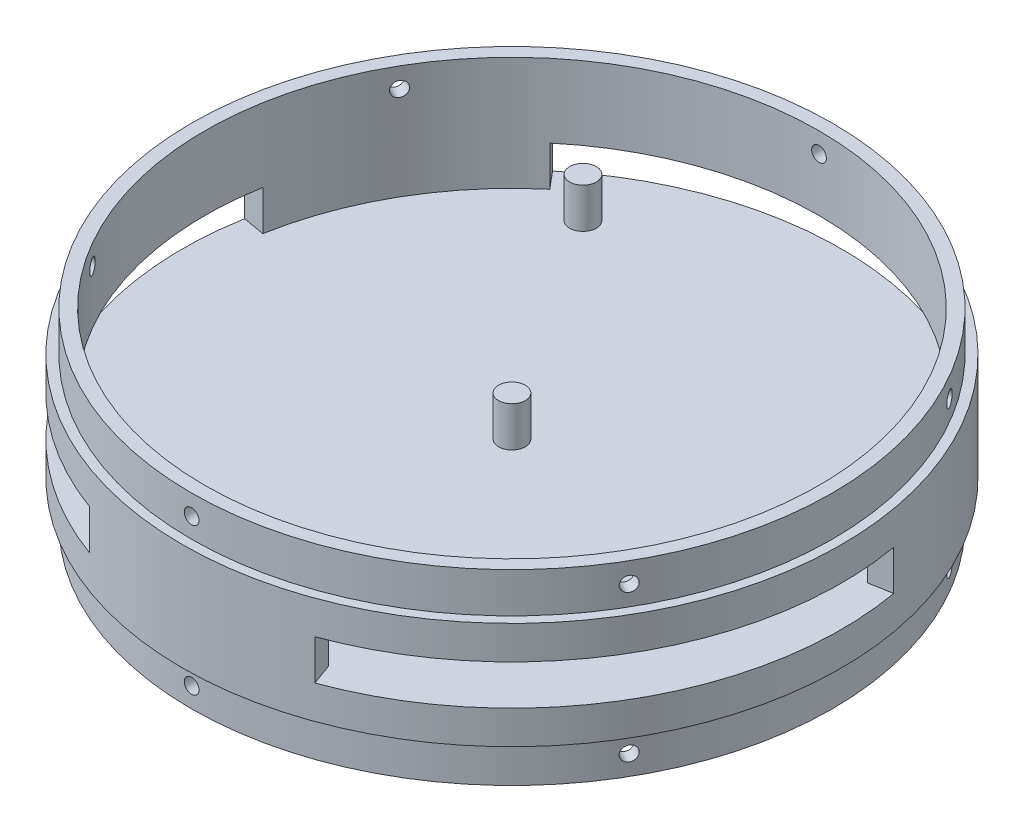
SolidWorks part; units mm, degrees
ref_plane "Front Plane" through (0, 0, 0) normal (0, 0, 1) x (1, 0, 0)
ref_plane "Top Plane" through (0, 0, 0) normal (0, 1, 0) x (1, 0, 0)
ref_plane "Right Plane" through (0, 0, 0) normal (1, 0, 0) x (0, 0, -1)
sketch "Sketch1" plane through (0, 0, 0) normal (0, 1, 0) x (1, 0, 0)
  line L0 (0, 0) -> (-50.3682, 60.0265)
  line L1 (0, 0) -> (50.3682, 60.0265)
  line L2 (0, 0) -> (0, 72.1431) construction
  circle A0 centre (0, 0) radius 78.359
  circle A1 centre (0, 0) radius 73.025
  circle A2 centre (0, 0) radius 76.1746
  dimension "D1" = 156.718
  dimension "D2" = 146.05
  dimension "D3" = 152.3492
  dimension "D4" = 80
extrude "Boss-Extrude1" add sketch "Sketch1" along normal blind 25.4 contours L2 A2 L1 A0 | L2 A1 L1 A2 | L2 A2 L1 A1 | L2 A0 L1 A2 | A2 L2 A1 L0 | A0 L2 A2 L0 | A2 L2 A0 L0 | A1 L2 A2 L0 region at (-31.7206, 0, 68.0251) region at (-47.1858, 0, -57.7895) region at (-33.0764, 0, 70.9325) region at (-48.8794, 0, -59.85)
ref_plane "Plane1" through (0, 12.7, 0) normal (0, 1, 0) x (1, 0, 0)
extrude "Boss-Extrude2" add sketch "Sketch1<3>" along normal blind 9.525 from surface contours A2 L2 A1 L0 | L2 A2 L1 A1 | L2 A1 L1 A2 | A1 L2 A2 L0 region at (-31.7206, 0, 68.0251) region at (-47.1858, 0, -57.7895) starting at face at (0, 25.4, 73.025)
sketch "Sketch1<3>" plane through (0, 0, 0) normal (0, 1, 0) x (1, 0, 0) same geometry as "Sketch1"
extrude "Boss-Extrude3" add sketch "Sketch1<4>" against normal blind 9.525 contours A2 L2 A1 L0 | A1 L2 A2 L0 | L2 A1 L1 A2 | L2 A2 L1 A1 region at (-31.7206, 0, 68.0251) region at (-47.1858, 0, -57.7895)
sketch "Sketch1<4>" plane through (0, 0, 0) normal (0, 1, 0) x (1, 0, 0) same geometry as "Sketch1"
ref_plane "Plane2" through (0, 0, -76.1746) normal (0, 0, -1) x (-1, 0, 0)
ref_axis "Axis1" through (0, 0, 0) along (0, 1, 0)
sketch "Sketch3" plane through (0, 0, -76.1746) normal (0, 0, -1) x (-1, 0, 0)
  line L0 (76.1746, 0) -> (-76.1746, 0) construction
  line L1 (-76.1746, -9.525) -> (76.1746, -9.525) construction
  line L2 (76.1746, 25.4) -> (-76.1746, 25.4) construction
  line L3 (76.1746, 34.925) -> (-76.1746, 34.925) construction
  line L4 (76.1746, 0) -> (-76.1746, 0)
  line L5 (-76.1746, -9.525) -> (76.1746, -9.525)
  line L6 (76.1746, 25.4) -> (-76.1746, 25.4)
  line L7 (76.1746, 34.925) -> (-76.1746, 34.925)
  line L8 (0, 34.925) -> (0, 25.4)
  line L9 (0, 0) -> (0, -9.525)
  circle A0 centre (0, 30.1625) radius 1.75
  circle A1 centre (0, -4.7625) radius 1.75
  point P12 (0, 30.1625)
  point P13 (0, -4.7625)
  point P14 (-77.5445, 179.1871)
  dimension "D1" = 3.5
extrude "Cut-Extrude2" cut sketch "Sketch3" against normal up to next contours L8 A0 | L8 A0 | L9 A1 | L9 A1 region at (-0.7427, 30.1625, -76.1746) region at (0.7427, 30.1625, -76.1746) region at (-0.7427, -4.7625, -76.1746) region at (0.7427, -4.7625, -76.1746)
extrude "Cut-Extrude3" cut sketch "Sketch1<7>" against normal mid plane 9.525 from surface contours L2 A1 L1 A2 | A1 L2 A2 L0 | A2 L2 A0 L0 | L2 A2 L1 A0 region at (-47.1858, 0, -57.7895) region at (-48.8794, 0, -59.85) starting at plane "Plane1"
sketch "Sketch1<7>" plane through (0, 0, 0) normal (0, 1, 0) x (1, 0, 0) same geometry as "Sketch1"
pattern_circular "CirPattern2" count 3 over 360 about axis through (0, 0, 0) along (0, 1, 0) of "Cut-Extrude3"
pattern_circular "CirPattern3" count 6 over 360 about axis through (0, 0, 0) along (0, 1, 0) of "Cut-Extrude2"
ref_plane "Plane3" through (0, 7.9375, 0) normal (0, 1, 0) x (1, 0, 0)
sketch "Sketch4" plane through (0, 7.9375, 0) normal (0, 1, 0) x (1, 0, 0)
  circle A0 centre (0, 0) radius 73.025
extrude "Boss-Extrude4" add sketch "Sketch4" against normal blind 6.35
sketch "Sketch5" plane through (0, 7.9375, 0) normal (0, 1, 0) x (1, 0, 0)
  line L0 (-50.3682, 60.0265) -> (-46.9396, 55.9404) construction
  line L1 (-36.5684, 53.4594) -> (0, 0) construction
  circle A0 centre (-36.5684, 53.4594) radius 3.175
  circle A2 centre (0, 0) radius 3.175
  point P9 (0, 0)
  dimension "D1" = 6.35
  dimension "D4" = 6.35
  dimension "D3" = 6.35
  dimension "D2" = 64.77
extrude "Boss-Extrude5" add sketch "Sketch5" along normal blind 9.525
pattern_circular "CirPattern4" count 3 over 360 about axis through (0, 7.9375, 0) along (0, 1, 0) of "Boss-Extrude5"
equation "\"AB_Coupler_OD_Length\"= 1in"
equation "\"AB_Coupling_Section_Length\"= 0.375in"
equation "\"AB_Coupler_Length\"= \"AB_Coupler_OD_Length\" + \"AB_Coupling_Section_Length\" * 2"
equation "\"D1@Boss-Extrude2\"=\"AB_Coupling_Section_Length\""
equation "\"D1@Boss-Extrude3\"=\"AB_Coupling_Section_Length\""
equation "\"D1@Boss-Extrude1\" = \"AB_Coupler_OD_Length\""
equation "\"Cutout_Angle\" = 80"
equation "\"AB_Coupler_Num_Screws\"= 6"
equation "\"Num_Cutouts\" = 3"
equation "\"D4@Sketch1\"=\"Cutout_Angle\""
equation "\"D1@CirPattern2\"=\"Num_Cutouts\""
equation "\"D1@CirPattern3\"=\"AB_Coupler_Num_Screws\""
equation "\"AB_Coupler_OD\"= 6.17in"
equation "\"AB_Coupler_ID\"= 5.75in"
equation "\"AB_Coupler_Surface_Diameter\"= 5.998in"
equation "\"D3@Sketch1\"=\"AB_Coupler_Surface_Diameter\""
equation "\"D2@Sketch1\"=\"AB_Coupler_ID\""
equation "\"D1@Sketch1\"=\"AB_Coupler_OD\""
equation "\"AB_Coupling_Screw_Diameter\"= 0.1065in"
equation "\"Aft_Section_Length\"= 40in"
equation "\"Aft_Lower_Length\"= 20in"
equation "\"Aft_Upper_Length\"= \"Aft_Section_Length\" - \"Aft_Lower_Length\" - \"AB_Coupler_OD_Length\""
equation "\"Mid_Coupler_Length\" = 10in"
equation "\"Lead_Screw_Dist\" = 2.25in"
equation "\"Lead_Screw_Diam\" = (27/64)*1in"
equation "\"Lead_Screw_Length\" = (\"Mid_Coupler_Length\" + 2*0.375in + 2*0.5in)"
equation "\"Bodytube_OD\" = 6.17in"
equation "\"Paddle_Pin_Offset\" = .25in"
equation "\"D3@Sketch5\"=\"Paddle_Pin_Offset\""
equation "\"D1@CirPattern4\"=\"Num_Cutouts\""
equation "\"Bodytube_ID\" = 5.998in"
equation "\"Paddle_Pin_Radius\" = 2.55in"
equation "\"D2@Sketch5\"=\"Paddle_Pin_Radius\""
